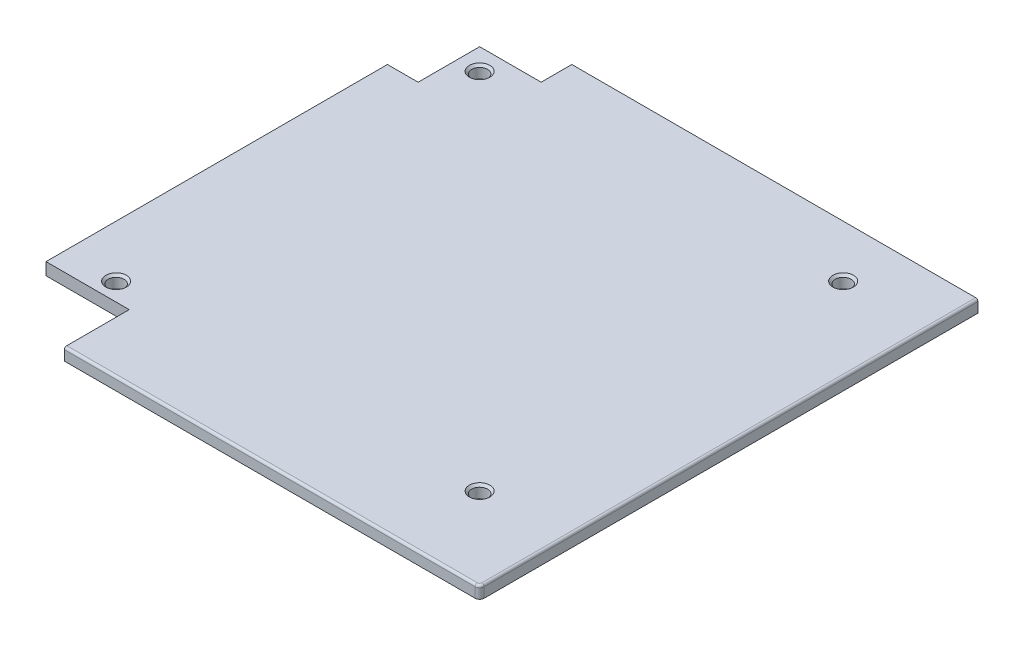
SolidWorks part; units mm, degrees
ref_plane "Front Plane" through (0, 0, 0) normal (0, 0, 1) x (1, 0, 0)
ref_plane "Top Plane" through (0, 0, 0) normal (0, 1, 0) x (1, 0, 0)
ref_plane "Right Plane" through (0, 0, 0) normal (1, 0, 0) x (0, 0, -1)
sketch "Sketch1" plane through (0, 0, 0) normal (0, 1, 0) x (1, 0, 0)
  line L0 (0, -76.2) -> (0, 76.2) construction
  line L1 (-66.25, -66.25) -> (66.25, -66.25) construction
  line L2 (-66.25, -66.25) -> (-66.25, 66.25) construction
  line L3 (-66.25, 66.25) -> (66.25, 66.25) construction
  line L4 (66.25, -66.25) -> (66.25, 66.25) construction
  line L5 (-66.25, -66.25) -> (66.25, 66.25) construction
  line L6 (-66.25, 66.25) -> (66.25, -66.25) construction
  line L11 (-66.2, 46.15) -> (-76.2, 46.15)
  line L12 (-46.15, 66.2) -> (-46.15, 76.2)
  line L15 (-46.15, 76.2) -> (86.25, 76.2)
  line L16 (86.25, 76.2) -> (86.25, -84.75)
  line L17 (84.75, -86.25) -> (-49.08, -86.25)
  line L18 (-76.2, -65.15) -> (-76.2, 46.15)
  line L19 (-66.2, 46.15) -> (-66.2, 66.2)
  line L20 (-66.2, 66.2) -> (-46.15, 66.2)
  line L21 (-49.08, -86.25) -> (-49.08, -65.15)
  line L22 (-49.08, -65.15) -> (-76.2, -65.15)
  circle A0 centre (-59.25, 59.25) radius 1.85
  circle A1 centre (-59.25, -59.25) radius 1.85
  circle A3 centre (59.25, -59.25) radius 1.85
  circle A4 centre (59.25, 59.25) radius 1.85
  circle A5 centre (-59.25, 59.25) radius 2.6
  circle A6 centre (59.25, 59.25) radius 2.6
  circle A7 centre (59.25, -59.25) radius 2.6
  circle A8 centre (-59.25, -59.25) radius 2.6
  arc A9 (86.25, -84.75) -> (84.75, -86.25) centre (84.75, -84.75) cw
  point P0 (0, 0)
  point P16 (0, 0)
  dimension "D2" = 3.7
  dimension "D3" = 7
  dimension "D7" = 20
  dimension "D9" = 5.2
  dimension "D10" = 1.5
  dimension "D1" = 132.5
  dimension "D4" = 9.95
  dimension "D5" = 20
  dimension "D6" = 20.1
  dimension "D8" = 9.95
  dimension "D11" = 10
  dimension "D12" = 21.1
  dimension "D13" = 27.12
extrude "Boss-Extrude1" add sketch "Sketch1" along normal mid plane 4 contours L18 L17 L16 L15 L12 L11 A8 A7 A6 A5 | A5 A0 | A6 A4 | A7 A3 | A8 A1 region at (7.9691, 0, 4.8317) region at (-61.7765, 0, -59.25) region at (56.7235, 0, -59.25) region at (56.7235, 0, 59.25) region at (-61.7765, 0, 59.25)
chamfer "Chamfer2" distance 1.5 angle 45 4 edges at (-59.25, 2, -57.4) (59.25, 2, -57.4) (-59.25, 2, 61.1) (59.25, 2, 61.1)
extrude "Cut-Extrude2" cut sketch "Sketch1<4>" along normal up to surface (2 mm away) from surface contours A5 A0 | A8 A1 | A7 A3 | A6 A4 region at (-61.7765, 0, -59.25) region at (56.7235, 0, -59.25) region at (56.7235, 0, 59.25) region at (-61.7765, 0, 59.25) up to face at (59.25, 2, -55.9) starting at face at (-19.7908, -2, 0.9782)
sketch "Sketch1<4>" plane through (0, 0, 0) normal (0, 1, 0) x (1, 0, 0) same geometry as "Sketch1"
fillet "Fillet1" radius 0.75 3 edges at (86.25, 2, 4.275) (85.8107, 2, 85.8107) (17.835, 2, 86.25)
